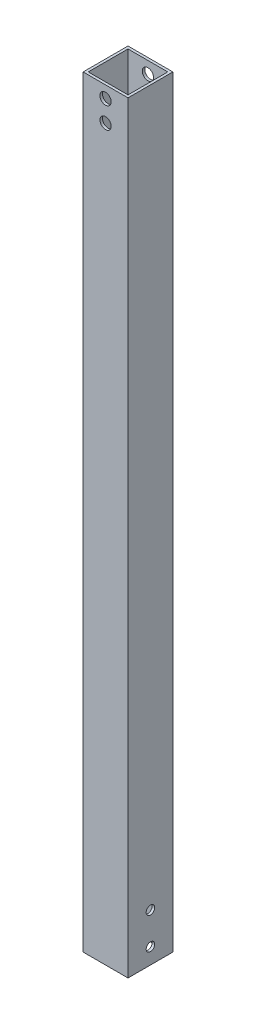
SolidWorks part; units mm, degrees
material "6061 Alloy"
ref_plane "Front Plane" through (0, 0, 0) normal (0, 0, 1) x (1, 0, 0)
ref_plane "Top Plane" through (0, 0, 0) normal (0, 1, 0) x (1, 0, 0)
ref_plane "Right Plane" through (0, 0, 0) normal (1, 0, 0) x (0, 0, -1)
sketch "Sketch1" plane through (0, 0, 0) normal (0, 1, 0) x (1, 0, 0)
  line L9 (12.7, -12.7) -> (-12.7, -12.7)
  line L10 (12.7, -12.7) -> (12.7, 12.7)
  line L11 (12.7, 12.7) -> (-12.7, 12.7)
  line L12 (-12.7, -12.7) -> (-12.7, 12.7)
  line L13 (12.7, -12.7) -> (-12.7, 12.7) construction
  line L14 (12.7, 12.7) -> (-12.7, -12.7) construction
  point P0 (0, 0)
  dimension "D1" = 25.4
extrude "Extrude-Thin1" add sketch "Sketch1" along normal blind 457.2 thin thin type mid plane wall 1.524
hole_wizard "1/4 Clearance Hole1" positions "Sketch2" profile "Sketch3" hole size "1/4" standard "ANSI Inch" end condition through all
sketch "Sketch2" plane through (0, 0, -13.462) normal (0, 0, -1) x (-1, 0, 0)
  point P0 (0, 450.0245)
  point P3 (0, 437.3245)
sketch "Sketch3" plane through (0, 450.0245, -13.462) normal (1, 0, 0) x (0, 1, 0)
  line L0 (0, 0) -> (0, 26.924)
  line L1 (0, 26.924) -> (3.3782, 26.924)
  line L2 (3.3782, 26.924) -> (3.3782, 0)
  line L5 (3.3782, 0) -> (0, 0)
  line L11 (0, -6.35) -> (0, 107.95) construction
  dimension "Thru Hole Dia." = 6.7564
  dimension "Thru Hole Depth" = 26.924
sketch "Sketch4" plane through (13.462, 0, 0) normal (1, 0, 0) x (0, 0, -1)
  line L0 (-13.462, 0) -> (13.462, 0) construction
  circle A0 centre (0, 9.525) radius 2.54
  circle A1 centre (0, 28.575) radius 2.54
  point P4 (0, 0)
  point P5 (0, 0)
  dimension "D1" = 5.08
  dimension "D2" = 9.525
  dimension "D3" = 28.575
hole_wizard "#10 Clearance Hole1" positions "Sketch5" profile "Sketch6" hole size "#10" standard "ANSI Inch" end condition through all
sketch "Sketch5" plane through (13.462, 0, 0) normal (1, 0, 0) x (0, 0, -1)
  point P0 (0, 9.525)
  point P3 (0, 28.575)
sketch "Sketch6" plane through (13.462, 9.525, 0) normal (0, 1, 0) x (0, 0, -1)
  line L0 (0, 0) -> (0, 26.924)
  line L1 (0, 26.924) -> (2.5527, 26.924)
  line L2 (2.5527, 26.924) -> (2.5527, 0)
  line L5 (2.5527, 0) -> (0, 0)
  line L11 (0, -6.35) -> (0, 107.95) construction
  dimension "Thru Hole Dia." = 5.1054
  dimension "Thru Hole Depth" = 26.924
